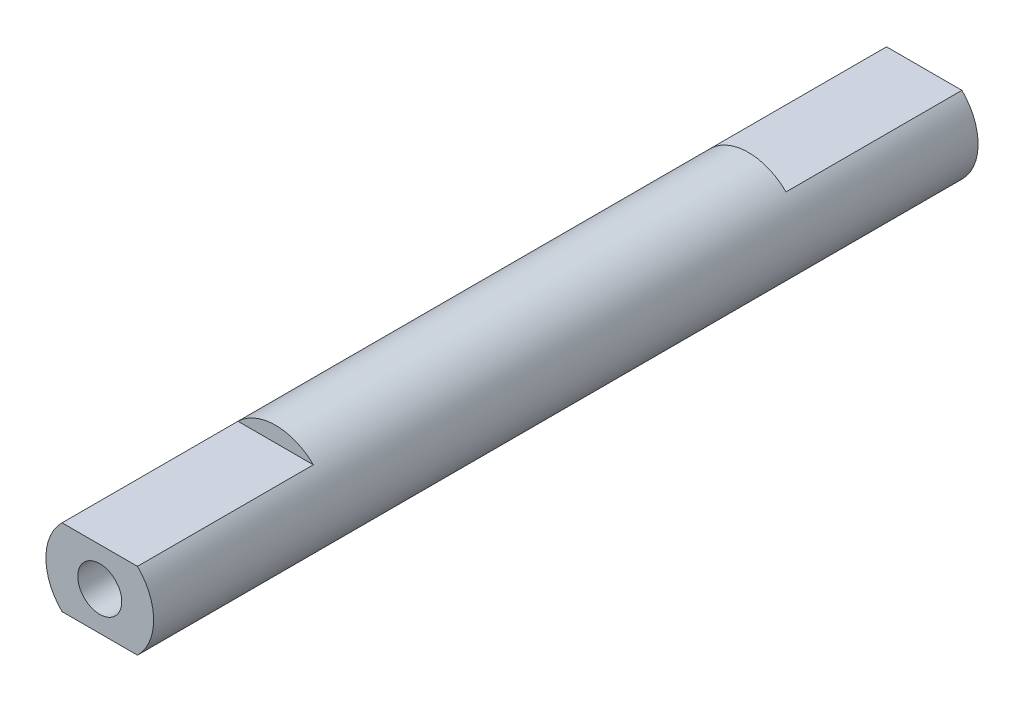
SolidWorks part; units mm, degrees
ref_plane "Alzado" through (0, 0, 0) normal (0, 0, 1) x (1, 0, 0)
ref_plane "Planta" through (0, 0, 0) normal (0, 1, 0) x (1, 0, 0)
ref_plane "Vista lateral" through (0, 0, 0) normal (1, 0, 0) x (0, 0, -1)
sketch "Croquis1" plane through (0, 0, 0) normal (0, 0, 1) x (1, 0, 0)
  circle A0 centre (0, 0) radius 2.45
  dimension "D1" = 4.9
extrude "Saliente-Extruir1" add sketch "Croquis1" along normal blind 18.75 and the other way blind 18.75
ref_plane "Plano1" through (0, 0, 10.74) normal (0, 0, 1) x (1, 0, 0)
sketch "Croquis3" plane through (0, 0, 18.75) normal (0, 0, 1) x (1, 0, 0)
  line L0 (0, 0) -> (0, 1.7086) construction
  line L1 (0, 0) -> (1.8187, 0) construction
  line L2 (-1.7146, 1.75) -> (1.7146, 1.75)
  line L3 (-1.7146, -1.75) -> (1.7146, -1.75)
  arc A0 (1.7146, 1.75) -> (-1.7146, 1.75) centre (0, 0) ccw
  arc A1 (-1.7146, -1.75) -> (1.7146, -1.75) centre (0, 0) ccw
  circle A2 centre (0, 0) radius 1
  point P9 (0, 1.75)
  dimension "D2" = 2
  dimension "D1" = 1.75
extrude "Cortar-Extruir1" cut sketch "Croquis3" against normal blind 8
mirror "Simetría1" about plane through (0, 0, 0) normal (0, 0, 1) of "Cortar-Extruir1"
